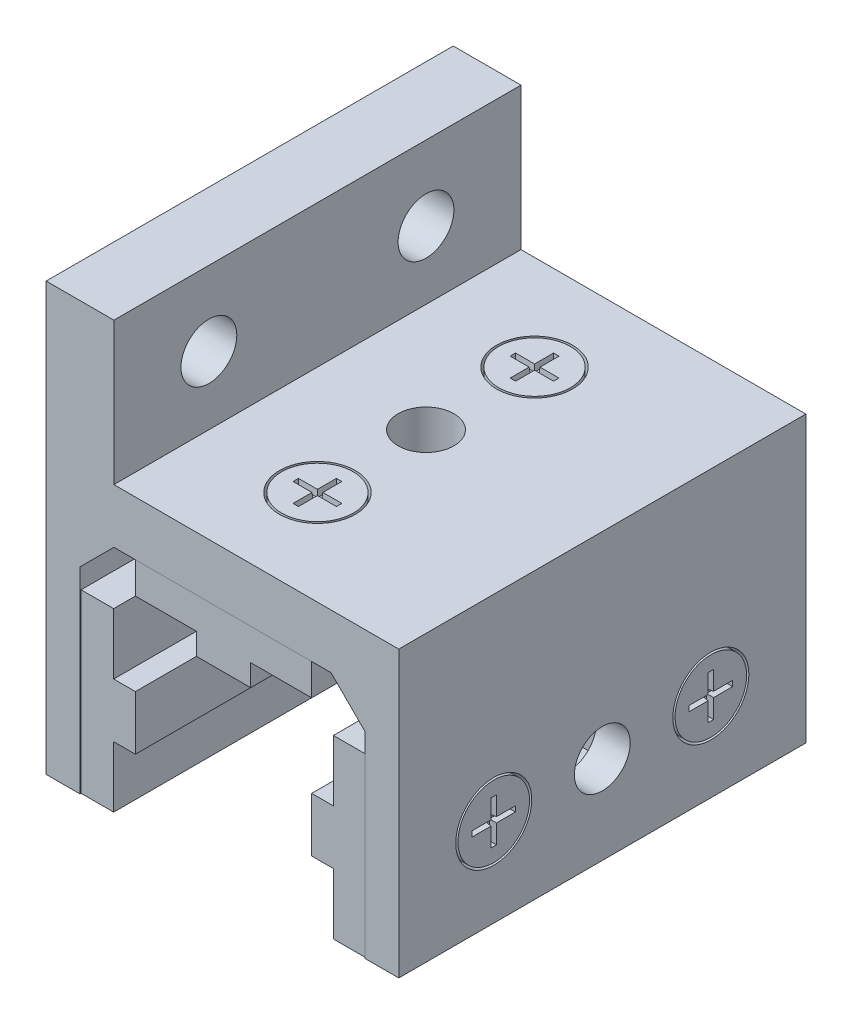
SolidWorks part; units mm, degrees
ref_plane "Front" through (0, 0, 0) normal (0, 0, 1) x (1, 0, 0)
ref_plane "Top" through (0, 0, 0) normal (0, 1, 0) x (1, 0, 0)
ref_plane "Right" through (0, 0, 0) normal (1, 0, 0) x (0, 0, -1)
sketch "Sketch1" plane through (0, 0, 0) normal (0, 0, 1) x (1, 0, 0)
  line L0 (-16.6624, 0) -> (-16.6624, 23.0124)
  line L1 (-20.6248, 33.3248) -> (20.6248, 33.3248)
  line L2 (-20.6248, 33.3248) -> (-20.6248, 0)
  line L3 (-20.6248, 0) -> (-16.6624, 0)
  line L4 (20.6248, 33.3248) -> (20.6248, 0)
  line L5 (-16.6624, 23.0124) -> (-12.7, 26.9748)
  line L6 (-12.7, 26.9748) -> (12.7, 26.9748)
  line L7 (12.7, 26.9748) -> (16.6624, 23.0124)
  line L8 (16.6624, 23.0124) -> (16.6624, 0)
  line L9 (16.6624, 0) -> (20.6248, 0)
  line L11 (-16.6624, 0) -> (16.6624, 0) construction
  dimension "Ht" = 33.3248
  dimension "Base Wd" = 41.2496
  dimension "D2" = 45
  dimension "Leg Thick" = 3.9624
  dimension "Top Thick" = 6.35
  dimension "Peak Wd" = 25.4
extrude "Boss-Extrude1" add sketch "Sketch1" along normal mid plane 47.625
sketch "Sketch2" plane through (0, 0, 0) normal (0, 0, 1) x (1, 0, 0)
  line L0 (-12.8524, 13.4874) -> (-12.8524, 20.6248)
  line L1 (-16.6624, 0) -> (-12.8524, 0)
  line L2 (-16.6624, 0) -> (-16.6624, 20.6248)
  line L3 (-16.6624, 20.6248) -> (-12.8524, 20.6248)
  line L4 (-12.8524, 0) -> (-12.8524, 7.1374)
  line L5 (-12.8524, 13.4874) -> (-10.3124, 13.4874)
  line L7 (-12.8524, 7.1374) -> (-10.3124, 7.1374)
  line L8 (-10.3124, 13.4874) -> (-10.3124, 7.1374)
  line L12 (-12.7, 26.9748) -> (12.7, 26.9748) construction
  line L13 (-10.3124, 26.9748) -> (10.3124, 26.9748)
  line L14 (-10.3124, 26.9748) -> (-10.3124, 23.1648)
  line L15 (-10.3124, 23.1648) -> (-3.175, 23.1648)
  line L16 (10.3124, 26.9748) -> (10.3124, 23.1648)
  line L17 (3.175, 23.1648) -> (10.3124, 23.1648)
  line L19 (-3.175, 23.1648) -> (-3.175, 20.6248)
  line L20 (-3.175, 20.6248) -> (3.175, 20.6248)
  line L21 (3.175, 23.1648) -> (3.175, 20.6248)
  point P14 (-10.3124, 10.3124)
  point P28 (0, 26.9748)
  dimension "Pad Wd" = 20.6248
  dimension "Pad Thick 1" = 6.35
  dimension "Pad Thick 2" = 3.81
  dimension "Pad Nose" = 6.35
extrude "Boss-Extrude2" add sketch "Sketch2" along normal mid plane 47.371 separate body
sketch "Sketch11" plane through (-10.3124, 0, 0) normal (1, 0, 0) x (0, 0, -1)
  line L0 (-23.6855, 13.4874) -> (23.6855, 13.4874) construction
  line L1 (-3.175, 13.4874) -> (3.175, 13.4874)
  line L2 (-3.175, 13.4874) -> (-3.175, 7.1374)
  line L3 (-3.175, 7.1374) -> (3.175, 7.1374)
  line L4 (3.175, 13.4874) -> (3.175, 7.1374)
  line L5 (-23.6855, 7.1374) -> (23.6855, 7.1374) construction
  point P8 (0, 13.4874)
extrude "Cut-Extrude5" cut sketch "Sketch11" against normal through all
sketch "Sketch12" plane through (0, 20.6248, 0) normal (0, -1, 0) x (1, 0, 0)
  line L0 (-3.175, 23.6855) -> (-3.175, -23.6855) construction
  line L1 (-3.175, 3.175) -> (3.175, 3.175)
  line L2 (-3.175, 3.175) -> (-3.175, -3.175)
  line L3 (-3.175, -3.175) -> (3.175, -3.175)
  line L4 (3.175, 3.175) -> (3.175, -3.175)
  line L5 (3.175, 23.6855) -> (3.175, -23.6855) construction
  point P8 (-3.175, 0)
extrude "Cut-Extrude6" cut sketch "Sketch12" against normal through all
mirror "Mirror1" about plane through (0, 0, 0) normal (1, 0, 0) of bodies 126 109
sketch "Sketch3" plane through (0, 33.3248, 0) normal (0, 1, 0) x (1, 0, 0)
  line L0 (0, -12.7) -> (0, 12.7) construction
  circle A0 centre (0, -12.7) radius 4.445
  circle A1 centre (0, -12.7) radius 4.191
  dimension "D1" = 0.254
  dimension "Screw Head Dia" = 8.89
  dimension "Screw Spacing" = 25.4
extrude "Cut-Extrude1" cut sketch "Sketch3" against normal blind 3.175
sketch "Sketch5" plane through (0, 33.3248, 0) normal (0, 1, 0) x (1, 0, 0)
  line L0 (0.3175, -12.3825) -> (2.54, -12.3825)
  line L1 (-0.3175, -10.16) -> (0.3175, -10.16)
  line L2 (-0.3175, -10.16) -> (-0.3175, -12.3825)
  line L3 (-0.3175, -15.24) -> (0.3175, -15.24)
  line L4 (0.3175, -10.16) -> (0.3175, -12.3825)
  line L5 (-2.54, -12.3825) -> (-0.3175, -12.3825)
  line L6 (-2.54, -12.3825) -> (-2.54, -13.0175)
  line L7 (-2.54, -13.0175) -> (-0.3175, -13.0175)
  line L8 (2.54, -12.3825) -> (2.54, -13.0175)
  line L9 (-0.3175, -13.0175) -> (-0.3175, -15.24)
  line L10 (0.3175, -13.0175) -> (0.3175, -15.24)
  line L11 (0.3175, -13.0175) -> (2.54, -13.0175)
  line L12 (-0.3175, -12.3825) -> (0.3175, -13.0175) construction
  dimension "D1" = 0.635
  dimension "D2" = 5.08
extrude "Cut-Extrude2" cut sketch "Sketch5" against normal blind 0.762 draft 5
sketch "Sketch13" plane through (20.6248, 0, 0) normal (1, 0, 0) x (0, 0, -1)
  circle A0 centre (-12.7, 10.3124) radius 4.445
  dimension "D1" = 8.89
extrude "Cut-Extrude-Thin1" cut sketch "Sketch13" against normal blind 1.9812 thin thin type one direction reverse wall 0.254
sketch "Sketch14" plane through (20.6248, 0, 0) normal (1, 0, 0) x (0, 0, -1)
  line L0 (-13.0175, 9.9949) -> (-13.0175, 7.7724)
  line L1 (-13.0175, 12.8524) -> (-12.3825, 12.8524)
  line L2 (-13.0175, 12.8524) -> (-13.0175, 10.6299)
  line L3 (-13.0175, 7.7724) -> (-12.3825, 7.7724)
  line L4 (-12.3825, 12.8524) -> (-12.3825, 10.6299)
  line L5 (-15.24, 10.6299) -> (-13.0175, 10.6299)
  line L6 (-15.24, 10.6299) -> (-15.24, 9.9949)
  line L7 (-15.24, 9.9949) -> (-13.0175, 9.9949)
  line L8 (-10.16, 10.6299) -> (-10.16, 9.9949)
  line L9 (-12.3825, 10.6299) -> (-10.16, 10.6299)
  line L10 (-12.3825, 9.9949) -> (-12.3825, 7.7724)
  line L11 (-12.3825, 9.9949) -> (-10.16, 9.9949)
  line L12 (-13.0175, 10.6299) -> (-12.3825, 9.9949) construction
  dimension "D1" = 0.635
  dimension "D2" = 5.08
extrude "Cut-Extrude7" cut sketch "Sketch14" against normal blind 0.762 draft 5
mirror "Mirror4" about plane through (0, 0, 0) normal (1, 0, 0) of "Cut-Extrude7", "Cut-Extrude-Thin1"
mirror "Mirror3" about plane through (0, 0, 0) normal (0, 0, 1) of "Mirror4", "Cut-Extrude-Thin1", "Cut-Extrude7", "Cut-Extrude1", "Cut-Extrude2"
sketch "Sketch9" plane through (0, 33.3248, 0) normal (0, 1, 0) x (1, 0, 0)
  circle A0 centre (0, 0) radius 3.2639
  dimension "Top Hole Dia" = 6.5278
extrude "Cut-Extrude4" cut sketch "Sketch9" against normal through all
sketch "Sketch15" plane through (0, 0, 0) normal (1, 0, 0) x (0, 0, -1)
  circle A0 centre (0, 10.3124) radius 3.2639
  dimension "Side Wall Hole Dia" = 6.5278
extrude "Cut-Extrude8" cut sketch "Sketch15" against normal through all and the other way through all
sketch "Sketch6" plane through (0, 0, 0) normal (0, 0, 1) x (1, 0, 0)
  line L0 (-20.6248, 0) -> (-16.6624, 0) construction
  line L1 (-20.6248, 26.9748) -> (-12.7, 26.9748)
  line L2 (-20.6248, 26.9748) -> (-20.6248, 49.9872)
  line L3 (-20.6248, 49.9872) -> (-12.7, 49.9872)
  line L4 (-12.7, 26.9748) -> (-12.7, 49.9872)
  line L5 (-12.7, 26.9748) -> (12.7, 26.9748) construction
  line L6 (-20.6248, 33.3248) -> (-20.6248, 0) construction
  dimension "Oall Ht" = 49.9872
  dimension "Side Flange Thickness" = 7.9248
extrude "Side Flange" add sketch "Sketch6" along normal up to surface (23.8125 mm away) and the other way up to surface (23.8125 mm away) up to face at (0, 16.6624, 23.8125) other way up to face at (0, 16.6624, -23.8125)
sketch "Sketch7" plane through (0, 0, 0) normal (1, 0, 0) x (0, 0, -1)
  line L0 (-12.7, 41.275) -> (12.7, 41.275) construction
  line L2 (-23.8125, 0) -> (23.8125, 0) construction
  line L3 (-12.7, 30.1498) -> (-12.7, 33.3248) construction
  circle A0 centre (-12.7, 41.275) radius 3.2639
  circle A1 centre (12.7, 41.275) radius 3.2639
  point P4 (0, 41.275)
  dimension "Side Flange Hole Dia" = 6.5278
  dimension "Side Flange Hole Spacing" = 41.275
extrude "Side Flange Hole" cut sketch "Sketch7" against normal through all
sketch "Sketch16" plane through (0, 0, 0) normal (0, 0, 1) x (1, 0, 0)
  line L1 (-20.6248, 33.3248) -> (-18.6436, 33.3248)
  line L2 (-20.6248, 33.3248) -> (-20.6248, 25.4)
  line L3 (-20.6248, 25.4) -> (-18.6436, 25.4)
  line L4 (-18.6436, 33.3248) -> (-18.6436, 25.4)
  line L5 (20.6248, 33.3248) -> (-12.7, 33.3248) construction
  line L6 (18.6436, 33.3248) -> (20.6248, 33.3248)
  line L7 (18.6436, 33.3248) -> (18.6436, 25.4)
  line L8 (18.6436, 25.4) -> (20.6248, 25.4)
  line L9 (20.6248, 33.3248) -> (20.6248, 25.4)
  line L10 (-20.6248, 0) -> (-16.6624, 0) construction
  line L11 (16.6624, 0) -> (20.6248, 0) construction
  point P4 (-18.6436, 0)
  point P13 (18.6436, 0)
  dimension "Oall Wd" = 41.2496
  dimension "Top Flange Thickness" = 7.9248
extrude "Top Flange" add sketch "Sketch16" along normal up to surface (23.8125 mm away) and the other way up to surface (23.8125 mm away) up to face at (-2.1167, 22.2165, 23.8125) other way up to face at (-2.1167, 22.2165, -23.8125)
sketch "Sketch17" plane through (0, 33.3248, 0) normal (0, 1, 0) x (1, 0, 0)
  line L0 (-28.575, 12.7) -> (28.575, -12.7) construction
  line L1 (-28.575, 12.7) -> (28.575, 12.7) construction
  line L2 (-28.575, 12.7) -> (-28.575, -12.7) construction
  line L3 (-28.575, -12.7) -> (28.575, -12.7) construction
  line L4 (28.575, 12.7) -> (28.575, -12.7) construction
  line L5 (-18.6436, 12.7) -> (-20.6248, 12.7) construction
  circle A0 centre (28.575, 12.7) radius 3.2639
  circle A1 centre (28.575, -12.7) radius 3.2639
  circle A2 centre (-28.575, 12.7) radius 3.2639
  circle A3 centre (-28.575, -12.7) radius 3.2639
  dimension "Top Flange Hole Dia" = 6.5278
  dimension "Top Flange Hole Spacing" = 57.15
extrude "Top Flange Hole" [suppressed] cut sketch "Sketch17" against normal through all
mirror "Mirror7" [suppressed] of bodies 126 128 114
mirror "Mirror6" [suppressed] of bodies 134
other "Delete Hole Short" [suppressed]
other "Delete Hole Long" [suppressed]
ref_axis "Axis1" through (0, 26.9748, 0) along (0, 1, 0)
equation "\"D1@Cut-Extrude1\" = \"Top Thick@Sketch1\" * .5"
equation "\"D1@Sketch13\" = \"Screw Head Dia@Sketch3\""
equation "\"D1@Cut-Extrude-Thin1\" = \"Leg Thick@Sketch1\" * .5"
equation "\"D5@Cut-Extrude-Thin1\" = \"D1@Sketch3\""
equation "\"D1@Cut-Extrude7\" = \"D1@Cut-Extrude2\""
equation "\"D1@Sketch14\" = \"D1@Sketch5\""
equation "\"D2@Sketch14\" = \"D2@Sketch5\""
equation "\"D3@Cut-Extrude7\" = \"D3@Cut-Extrude2\""
